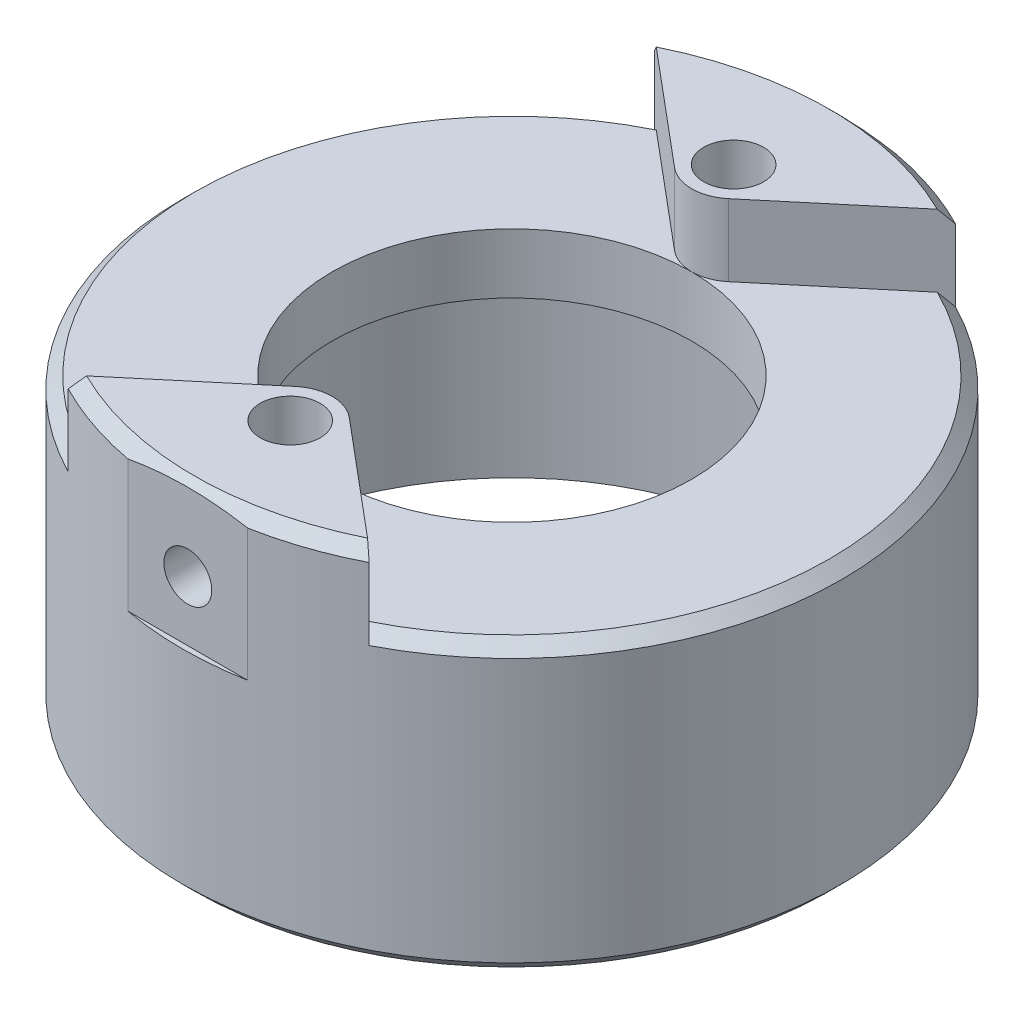
SolidWorks part; units mm, degrees
ref_plane "Front Plane" through (0, 0, 0) normal (0, 0, 1) x (1, 0, 0)
ref_plane "Top Plane" through (0, 0, 0) normal (0, 1, 0) x (1, 0, 0)
ref_plane "Right Plane" through (0, 0, 0) normal (1, 0, 0) x (0, 0, -1)
sketch "Sketch1" plane through (0, 0, 0) normal (0, 0, 1) x (1, 0, 0)
  line L0 (0, 0) -> (0, 54.0947) construction
sketch "Sketch2" plane through (0, 0, 0) normal (0, 1, 0) x (1, 0, 0)
  circle A0 centre (0, 0) radius 15
  circle A1 centre (0, 0) radius 27.5
  circle A2 centre (0, 18.5) radius 2.5
  circle A3 centre (0, -18.5) radius 2.5
  point P8 (0, 0)
  point P9 (0, 0)
  point P10 (0, 0)
  dimension "D1" = 30
  dimension "D2" = 55
  dimension "D5" = 5
  dimension "D6" = 5
  dimension "D3" = 37
  dimension "D4" = 18.5
extrude "Boss-Extrude1" add sketch "Sketch2" along normal blind 30
sketch "Sketch3" plane through (0, 0, 0) normal (0, -1, 0) x (1, 0, 0)
  circle A0 centre (0, 0) radius 23.5
  dimension "D1" = 47
extrude "Cut-Extrude1" cut sketch "Sketch3" against normal blind 19
sketch "Sketch4" plane through (0, 30, 0) normal (0, 1, 0) x (1, 0, 0)
  line L0 (-2.2498, -15.8188) -> (-12.5556, -24.4665)
  line L1 (2.2498, -15.8188) -> (12.5556, -24.4665)
  line L2 (0, 0) -> (0, 12.6465) construction
  line L3 (0, 0) -> (19.0604, 0) construction
  line L4 (-2.2498, 15.8188) -> (-12.5556, 24.4665)
  line L5 (2.2498, 15.8188) -> (12.5556, 24.4665)
  line L6 (-5, -27.0416) -> (5, -27.0416)
  line L10 (-5, 27.0416) -> (5, 27.0416)
  arc A0 (2.2498, -15.8188) -> (-2.2498, -15.8188) centre (0, -18.5) ccw
  arc A1 (-2.2498, 15.8188) -> (2.2498, 15.8188) centre (0, 18.5) ccw
  circle A2 centre (0, 0) radius 27.5 construction
  circle A3 centre (0, 0) radius 15 construction
  arc A4 (12.5556, -24.4665) -> (12.5556, 24.4665) centre (0, 0) ccw
  arc A5 (-12.5556, 24.4665) -> (-12.5556, -24.4665) centre (0, 0) ccw
  arc A6 (-5, -27.0416) -> (5, -27.0416) centre (0, 0) ccw
  arc A9 (-5, 27.0416) -> (5, 27.0416) centre (0, 0) cw
  dimension "D1" = 100
  dimension "D2" = 50
  dimension "D3" = 10
sketch "Sketch5" plane through (0, 30, 0) normal (0, 1, 0) x (1, 0, 0)
extrude "Cut-Extrude2" cut sketch "Sketch4" against normal blind 6 contours L5 A4 L1 A0 L0 A5 L4 A1
sketch "Sketch6" plane through (0, 24, 0) normal (0, 1, 0) x (1, 0, 0)
  line L0 (-5, -27.0416) -> (5, -27.0416)
  line L1 (0, 0) -> (16.49, 0) construction
  line L2 (0, 0) -> (0, -12.4135) construction
  line L3 (-5, 27.0416) -> (5, 27.0416)
  arc A0 (-12.5556, -24.4665) -> (12.5556, -24.4665) centre (0, 0) ccw construction
  arc A1 (-5, -27.0416) -> (5, -27.0416) centre (0, 0) ccw
  arc A2 (-5, 27.0416) -> (5, 27.0416) centre (0, 0) cw
  point P8 (1.4716, -12.326)
  dimension "D1" = 10
  dimension "D2" = 5
extrude "Cut-Extrude3" cut sketch "Sketch6" against normal blind 6 and the other way blind 6
sketch "Sketch7" plane through (0, 0, -27.0416) normal (0, 0, -1) x (-1, 0, 0)
  line L0 (0, 0) -> (0, 54.0947) construction
  line L1 (5, 18) -> (-5, 18) construction
  circle A0 centre (0, 23) radius 2
  point P4 (0, 0)
  point P6 (0, 0)
  dimension "D1" = 4
  dimension "D2" = 5
extrude "Cut-Extrude4" cut sketch "Sketch7" against normal blind 5
mirror "Mirror1" about plane through (0, 0, 0) normal (0, 0, 1) of "Cut-Extrude4"
chamfer "Chamfer4" distance 1 angle 45 7 edges at (8.8717, 30, 26.0296) (-8.8717, 30, 26.0296) (-8.8717, 30, -26.0296) (8.8717, 30, -26.0296) (-27.5, 24, 0) (0, 0, 27.5) (27.5, 24, 0)
